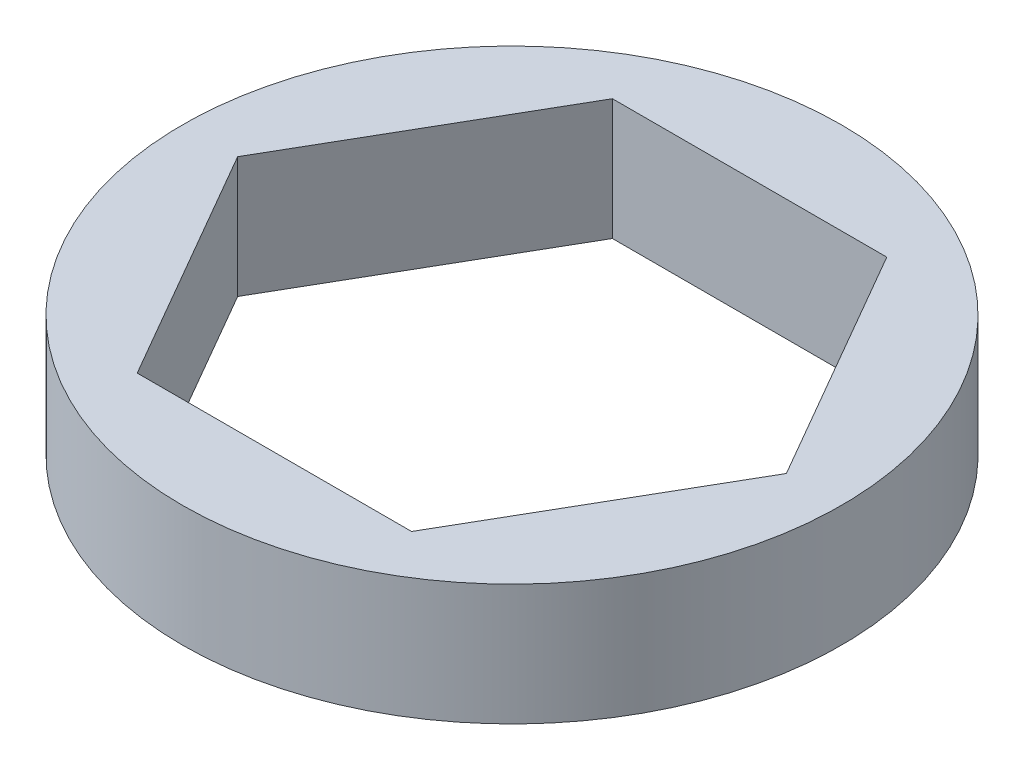
SolidWorks part; units mm, degrees
ref_plane "Front Plane" through (0, 0, 0) normal (0, 0, 1) x (1, 0, 0)
ref_plane "Top Plane" through (0, 0, 0) normal (0, 1, 0) x (1, 0, 0)
ref_plane "Right Plane" through (0, 0, 0) normal (1, 0, 0) x (0, 0, -1)
sketch "Sketch1" plane through (0, 0, 0) normal (0, 1, 0) x (1, 0, 0)
  line L1 (2.6763, -4.6355) -> (5.3526, 0)
  line L2 (5.3526, 0) -> (2.6763, 4.6355)
  line L3 (2.6763, 4.6355) -> (-2.6763, 4.6355)
  line L4 (-2.6763, 4.6355) -> (-5.3526, 0)
  line L5 (-5.3526, 0) -> (-2.6763, -4.6355)
  line L6 (-2.6763, -4.6355) -> (2.6763, -4.6355)
  circle A0 centre (0, 0) radius 6.4294
  circle A1 centre (0, 0) radius 4.6355 construction
  dimension "D1" = 9.271
  dimension "D2" = 12.8587
extrude "Boss-Extrude1" add sketch "Sketch1" along normal mid plane 2.3622
